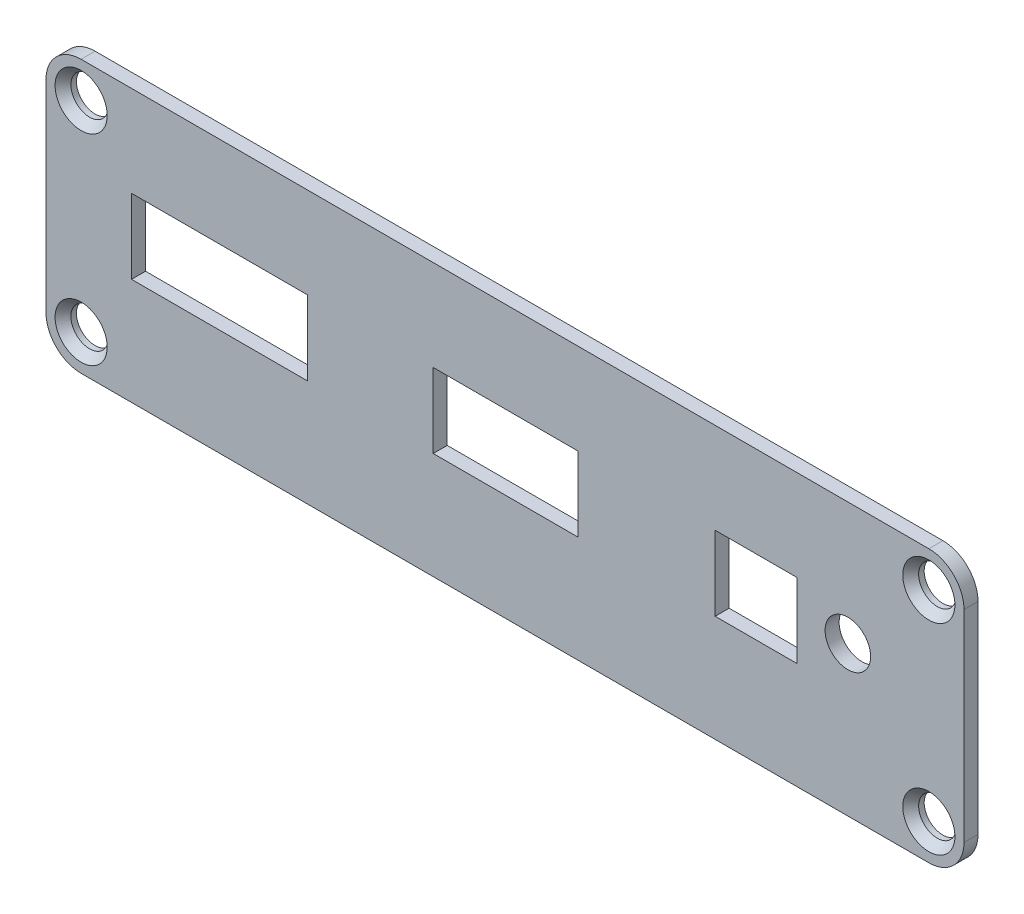
SolidWorks part; units mm, degrees
ref_plane "Front Plane" through (0, 0, 0) normal (0, 0, 1) x (1, 0, 0)
ref_plane "Top Plane" through (0, 0, 0) normal (0, 1, 0) x (1, 0, 0)
ref_plane "Right Plane" through (0, 0, 0) normal (1, 0, 0) x (0, 0, -1)
sketch "Sketch1" plane through (0, 0, 0) normal (0, 0, 1) x (1, 0, 0)
  line L1 (0, 0) -> (102.87, 0)
  line L2 (0, 0) -> (0, 30.48)
  line L3 (0, 30.48) -> (102.87, 30.48)
  line L4 (102.87, 0) -> (102.87, 30.48)
  dimension "D1" = 102.87
  dimension "D2" = 30.48
extrude "Boss-Extrude1" add sketch "Sketch1" along normal blind 1.57
fillet "Fillet1" radius 3.935 4 edges at (0, 0, 0.785) (102.87, 0, 0.785) (102.87, 30.48, 0.785) (0, 30.48, 0.785)
hole_wizard "CSK for #6 Flat Head Machine Screw1" positions "Sketch3" profile "Sketch4" countersink size "#6" standard "ANSI Inch" end condition through all
sketch "Sketch3" plane through (0, 0, 1.57) normal (0, 0, 1) x (1, 0, 0)
  line L0 (0, 26.545) -> (0, 3.935) construction
  line L1 (98.935, 30.48) -> (3.935, 30.48) construction
  line L2 (3.935, 0) -> (98.935, 0) construction
  line L3 (102.87, 3.935) -> (102.87, 26.545) construction
  point P0 (3.937, 26.4795)
  point P8 (3.937, 4.0005)
  point P10 (98.933, 26.4795)
  point P12 (98.933, 4.0005)
  dimension "D1" = 3.937
  dimension "D2" = 4.0005
  dimension "D3" = 3.937
  dimension "D4" = 4.0005
  dimension "D5" = 3.937
  dimension "D6" = 4.0005
  dimension "D7" = 4.0005
  dimension "D8" = 3.937
sketch "Sketch4" plane through (3.937, 26.4795, 1.57) normal (1, 0, 0) x (0, -1, 0)
  line L0 (0, 0) -> (0, 1.57)
  line L1 (0, 1.57) -> (2.0955, 1.57)
  line L2 (2.0955, 1.57) -> (2.0955, 0.9496)
  line L3 (2.0955, 0.9496) -> (2.921, 0)
  line L5 (2.921, 0) -> (0, 0)
  line L6 (-2.0955, 0.9496) -> (-2.921, 0) construction
  line L11 (0, -6.35) -> (0, 107.95) construction
  dimension "Thru Hole Dia." = 4.191
  dimension "Thru Hole Depth" = 1.57
  dimension "Near C'Sink Dia." = 5.842
  dimension "Near C'Sink Angle" = 82
sketch "data side" [suppressed] plane through (0, 0, 0) normal (0, 0, 1) x (1, 0, 0)
  line L0 (1.435, 10.7795) -> (0, 10.7795) construction
  line L1 (1.435, 10.7795) -> (101.435, 10.7795) construction
  line L2 (1.435, 10.7795) -> (1.435, 12.3495) construction
  line L3 (1.435, 12.3495) -> (101.435, 12.3495) construction
  line L4 (101.435, 10.7795) -> (101.435, 12.3495) construction
  line L6 (101.435, 10.7795) -> (102.87, 10.7795) construction
  line L8 (102.87, 3.935) -> (102.87, 26.545) construction
  line L21 (0, 26.545) -> (0, 3.935) construction
  line L22 (3.935, 0) -> (98.935, 0) construction
  line L23 (46.965, 14.0295) -> (55.905, 14.0295) construction
  line L24 (48.265, 15.7095) -> (54.605, 15.7095)
  line L25 (46.965, 14.4095) -> (46.965, 13.6495)
  line L26 (48.265, 12.3495) -> (54.605, 12.3495)
  line L27 (55.905, 14.4095) -> (55.905, 13.6495)
  line L28 (51.435, 12.3495) -> (51.435, 15.7095) construction
  line L29 (46.965, 15.7095) -> (0, 15.7095) construction
  line L30 (55.905, 15.7095) -> (102.87, 15.7095) construction
  arc A1 (54.605, 12.3495) -> (55.905, 13.6495) centre (54.605, 13.6495) ccw
  arc A2 (54.605, 15.7095) -> (55.905, 14.4095) centre (54.605, 14.4095) cw
  arc A3 (46.965, 13.6495) -> (48.265, 12.3495) centre (48.265, 13.6495) ccw
  arc A4 (48.265, 15.7095) -> (46.965, 14.4095) centre (48.265, 14.4095) ccw
  circle A5 centre (16.435, 18.8995) radius 3.25
  circle A6 centre (87.435, 14.8495) radius 2.5
  point P32 (46.965, 12.3495)
  dimension "D4" = 5
  dimension "D5" = 2.5
  dimension "D6" = 6.5
  dimension "D10" = 1.3
  dimension "D13" = 14
  dimension "D2" = 1.57
  dimension "D3" = 100
  dimension "D7" = 8.94
  dimension "D8" = 3.36
  dimension "D11" = 6.55
  dimension "D12" = 15
  dimension "D14" = 10.7795
sketch "io side" plane through (0, 0, 1.57) normal (0, 0, 1) x (1, 0, 0)
  line L0 (1.435, 10.7795) -> (0, 10.7795) construction
  line L1 (1.435, 10.7795) -> (101.435, 10.7795) construction
  line L2 (1.435, 10.7795) -> (1.435, 12.3495) construction
  line L3 (1.435, 12.3495) -> (101.435, 12.3495) construction
  line L4 (101.435, 10.7795) -> (101.435, 12.3495) construction
  line L5 (0, 26.545) -> (0, 3.935) construction
  line L6 (101.435, 10.7795) -> (102.87, 10.7795) construction
  line L7 (102.87, 3.935) -> (102.87, 26.545) construction
  line L9 (75.385, 19.8995) -> (83.785, 19.8995)
  line L10 (75.385, 19.8995) -> (75.385, 12.3495)
  line L11 (75.385, 12.3495) -> (83.785, 12.3495)
  line L12 (83.785, 19.8995) -> (83.785, 12.3495)
  line L13 (43.79, 19.8995) -> (59.19, 19.8995)
  line L14 (43.79, 19.8995) -> (43.79, 12.3495)
  line L15 (43.79, 12.3495) -> (59.19, 12.3495)
  line L16 (59.19, 19.8995) -> (59.19, 12.3495)
  line L17 (9.985, 12.3495) -> (28.885, 12.3495)
  line L18 (9.985, 12.3495) -> (9.985, 19.8995)
  line L19 (9.985, 19.8995) -> (28.885, 19.8995)
  line L20 (28.885, 12.3495) -> (28.885, 19.8995)
  circle A0 centre (89.8563, 16.7478) radius 2.15
  dimension "D4" = 4.3983
  dimension "D5" = 11.5787
  dimension "D6" = 4.3
  dimension "D1" = 10.7795
  dimension "D2" = 1.57
  dimension "D3" = 100
  dimension "D7" = 8.4
  dimension "D8" = 7.55
  dimension "D9" = 17.65
  dimension "D10" = 15.4
  dimension "D11" = 18.9
  dimension "D12" = 42.245
  dimension "D13" = 72.55
sketch "Sketch6" plane through (0, 0, 1.57) normal (0, 0, 1) x (1, 0, 0)
  line L0 (75.385, 19.8995) -> (75.385, 12.3495) construction
  line L1 (75.385, 12.3495) -> (83.785, 12.3495) construction
  line L2 (83.785, 19.8995) -> (83.785, 12.3495) construction
  line L3 (75.385, 19.8995) -> (83.785, 19.8995) construction
  line L4 (59.19, 19.8995) -> (59.19, 12.3495) construction
  line L5 (43.79, 12.3495) -> (59.19, 12.3495) construction
  line L6 (43.79, 19.8995) -> (43.79, 12.3495) construction
  line L7 (43.79, 19.8995) -> (59.19, 19.8995) construction
  line L8 (9.985, 12.3495) -> (9.985, 19.8995) construction
  line L9 (9.985, 12.3495) -> (28.885, 12.3495) construction
  line L10 (28.885, 12.3495) -> (28.885, 19.8995) construction
  line L11 (9.985, 19.8995) -> (28.885, 19.8995) construction
  line L12 (75.385, 19.8995) -> (75.385, 12.3495)
  line L13 (75.385, 12.3495) -> (83.785, 12.3495)
  line L14 (83.785, 19.8995) -> (83.785, 12.3495)
  line L15 (75.385, 19.8995) -> (83.785, 19.8995)
  line L16 (59.19, 19.8995) -> (59.19, 12.3495)
  line L17 (43.79, 12.3495) -> (59.19, 12.3495)
  line L18 (43.79, 19.8995) -> (43.79, 12.3495)
  line L19 (43.79, 19.8995) -> (59.19, 19.8995)
  line L20 (9.985, 12.3495) -> (9.985, 19.8995)
  line L21 (9.985, 12.3495) -> (28.885, 12.3495)
  line L22 (28.885, 12.3495) -> (28.885, 19.8995)
  line L23 (9.985, 19.8995) -> (28.885, 19.8995)
  circle A0 centre (89.8563, 16.7478) radius 2.15 construction
  circle A1 centre (89.8563, 16.7478) radius 2.15
extrude "Cut-Extrude1" cut sketch "Sketch6" against normal through all
other "Move Face1" flip direction yes face at (19.435, 12.3495, 0.785) face at (51.49, 12.3495, 0.785) face at (79.585, 12.3495, 0.785) face at (92.0063, 16.7478, 0) face at (19.435, 19.8995, 0.785) face at (51.49, 19.8995, 0.785) face at (79.585, 19.8995, 0.785) face at (75.385, 16.1245, 0.785) face at (83.785, 16.1245, 0.785) face at (59.19, 16.1245, 0.785) face at (28.885, 16.1245, 0.785) face at (9.985, 16.1245, 0.785) face at (43.79, 16.1245, 0.785) offset 0.4 parameters "D1"=0.4
extrude "Cut-Extrude9" [suppressed] cut sketch "data side" along normal up to surface (1.57 mm away) up to face at (19.435, 16.1245, 1.57)
other "Move Face4" [suppressed] flip direction yes offset 0.5 parameters "D1"=0.5
equation "\"D3@Sketch3\"=\"D1@Sketch3\""
equation "\"D4@Sketch3\"=\"D2@Sketch3\""
equation "\"D5@Sketch3\"=\"D1@Sketch3\""
equation "\"D6@Sketch3\"=\"D2@Sketch3\""
equation "\"D7@Sketch3\"=\"D2@Sketch3\""
equation "\"D8@Sketch3\"=\"D1@Sketch3\""
